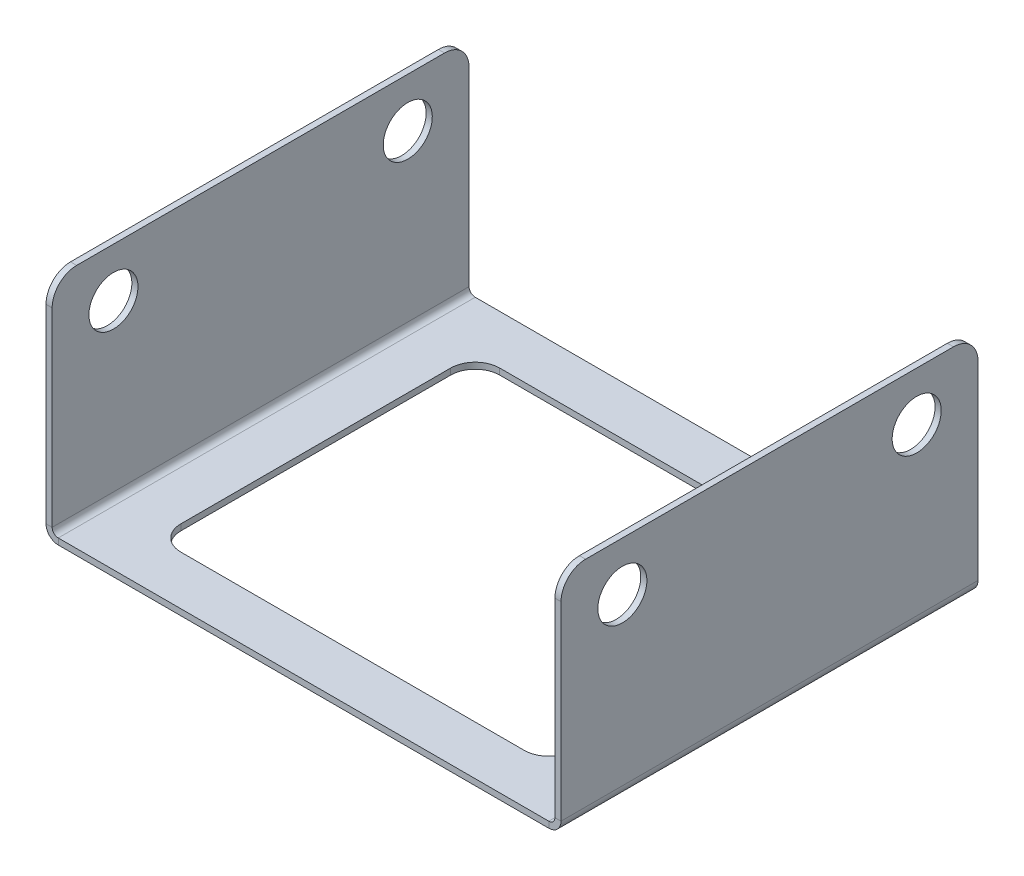
SolidWorks part; units mm, degrees
note: The reader was unsure of these and kept them because the rebuilt part matched: flange length of "Edge-Flange2", "Edge-Flange3".
ref_plane "Front Plane" through (0, 0, 0) normal (0, 0, 1) x (1, 0, 0)
ref_plane "Top Plane" through (0, 0, 0) normal (0, 1, 0) x (1, 0, 0)
ref_plane "Right Plane" through (0, 0, 0) normal (1, 0, 0) x (0, 0, -1)
sketch "Sketch1" plane through (0, 0, 0) normal (0, 1, 0) x (1, 0, 0)
  line L1 (-10, 8.5) -> (10, 8.5)
  line L2 (-10, 8.5) -> (-10, -8.5)
  line L3 (-10, -8.5) -> (10, -8.5)
  line L4 (10, 8.5) -> (10, -8.5)
  line L5 (-10, 8.5) -> (10, -8.5) construction
  line L6 (-10, -8.5) -> (10, 8.5) construction
  point P0 (0, 0)
base flange "Base-Flange1" sketch "Sketch1" thickness 0.25 reverse thickness direction no parameters "D1"=20
sketch "Sketch6" plane through (0, 0, 0) normal (0, 1, 0) x (1, 0, 0)
  line L1 (-7, 6.5) -> (7, 6.5)
  line L2 (-8, 5.5) -> (-8, -5.5)
  line L3 (-7, -6.5) -> (7, -6.5)
  line L4 (8, 5.5) -> (8, -5.5)
  line L5 (-8, 6.5) -> (8, -6.5) construction
  line L6 (-8, -6.5) -> (8, 6.5) construction
  arc A0 (-8, -5.5) -> (-7, -6.5) centre (-7, -5.5) ccw
  arc A1 (7, -6.5) -> (8, -5.5) centre (7, -5.5) ccw
  arc A2 (8, 5.5) -> (7, 6.5) centre (7, 5.5) ccw
  arc A3 (-7, 6.5) -> (-8, 5.5) centre (-7, 5.5) ccw
  point P0 (0, 0)
  dimension "D1" = 1
extrude "Cut-Extrude1" cut sketch "Sketch6" against normal through all normal cut yes
edge flange "Edge-Flange2" sketch "Sketch18" flange angle 90 flange length 9 flange position bend outside bend radius 0.25 thickness 0.25 parameters "D6"=10
sketch "Sketch18" plane through (10, 0, 0) normal (1, 0, 0) x (0, 0, -1)
  line L0 (-8.5, 0) -> (8.5, 0) construction
  line L1 (-8.5, 0) -> (8.5, 0)
  line L2 (-8.5, 0) -> (-8.5, 9)
  line L3 (-8.5, 9) -> (8.5, 9)
  line L4 (8.5, 9) -> (8.5, 0)
bend "EdgeBend1" bend radius 0.25 bend angle 90 parameters "D5"=1
edge flange "Edge-Flange3" sketch "Sketch23" flange angle 90 flange length 9 flange position bend outside bend radius 0.25 thickness 0.25 parameters "D6"=10
sketch "Sketch23" plane through (-10, 0, 0) normal (1, 0, 0) x (0, 0, -1)
  line L1 (8.5, 0) -> (-8.5, 0) construction
  line L2 (-8.5, 0) -> (-8.5, 9)
  line L3 (-8.5, 9) -> (8.5, 9)
  line L4 (8.5, 9) -> (8.5, 0)
  line L5 (8.5, 0) -> (-8.5, 0)
bend "EdgeBend2" bend radius 0.25 bend angle 90 parameters "D5"=2
fillet "Fillet1" radius 1 4 edges at (-10.375, 9, 8.5) (-10.375, 9, -8.5) (10.375, 9, -8.5) (10.375, 9, 8.5)
sketch "Sketch27" plane through (-10.5, 0, 0) normal (-1, 0, 0) x (0, 0, 1)
  line L0 (0, 9) -> (0, 10.9856) construction
  line L2 (0, 7) -> (3.9115, 7) construction
  line L3 (-6.6726, 9) -> (-10.6194, 9) construction
  line L6 (-5, 7) -> (-5, 10.8971) construction
  circle A0 centre (-6, 7) radius 1
  circle A1 centre (6, 7) radius 1
  dimension "D2" = 6
  dimension "D1" = 2
extrude "Cut-Extrude2" cut sketch "Sketch27" against normal through all normal cut yes
sketch "Bend-Lines1" [suppressed] plane through (0, 0, 0) normal (0, 1, 0) x (1, 0, 0)
sketch "Bounding-Box1" [suppressed] plane through (0, 0, 0) normal (0, 1, 0) x (1, 0, 0)
sheet metal parameters "Sheet-Metal(1)" thickness 0.25 parameters "D1"=20
flat pattern "Flat-Pattern(1)" [suppressed]
sketch "Bend-Lines2" plane through (0, 0, 0) normal (0, 1, 0) x (1, 0, 0)
sketch "Bounding-Box2" [suppressed] plane through (0, 0, 0) normal (0, 1, 0) x (1, 0, 0)
sheet metal parameters "Sheet-Metal(2)" thickness 0.25 parameters "D1"=20
flat pattern "Flat-Pattern(1)"
sketch "Bend-Lines3" plane through (0, 0, 0) normal (0, 1, 0) x (1, 0, 0)
sketch "Bounding-Box3" [suppressed] plane through (0, 0, 0) normal (0, 1, 0) x (1, 0, 0)
sheet metal parameters "Sheet-Metal(3)" thickness 0.25 parameters "D1"=20
flat pattern "Flat-Pattern(1)" [suppressed]
sketch "Bend-Lines4" plane through (0, 0, 0) normal (0, 1, 0) x (1, 0, 0)
sketch "Bounding-Box4" [suppressed] plane through (0, 0, 0) normal (0, 1, 0) x (1, 0, 0)
bend of the flat pattern "Flatten-<EdgeBend1>1"
sheet metal parameters "Sheet-Metal(4)" thickness 0.25 parameters "D1"=20
flat pattern "Flat-Pattern(1)" [suppressed]
sketch "Bend-Lines5" plane through (0, 0, 0) normal (0, 1, 0) x (1, 0, 0)
sketch "Bounding-Box5" [suppressed] plane through (0, 0, 0) normal (0, 1, 0) x (1, 0, 0)
bend of the flat pattern "Flatten-<EdgeBend1>2"
bend of the flat pattern "Flatten-<EdgeBend2>1"
sheet metal parameters "Sheet-Metal(5)" thickness 0.25 parameters "D1"=20
flat pattern "Flat-Pattern(1)"
sketch "Bend-Lines6" plane through (0, 0, 0) normal (0, 1, 0) x (1, 0, 0)
  line L0 (-10.2945, 8.5) -> (-10.2945, -8.5) construction
  line L1 (10.2945, -8.5) -> (10.2945, 8.5) construction
  line L2 (-10.2945, 8.5) -> (-10.2945, -8.5) construction
  line L3 (10.2945, -8.5) -> (10.2945, 8.5) construction
sketch3d "Bounding-Box6" [suppressed]
  line L0 (19.339, -8.5, 0) -> (-19.339, -8.5, 0) construction
  line L1 (19.339, 8.5, 0) -> (-19.339, 8.5, 0) construction
  line L2 (19.339, -8.5, 0) -> (19.339, 8.5, 0) construction
  line L3 (-19.339, -8.5, 0) -> (-19.339, 8.5, 0) construction
bend of the flat pattern "Flatten-<EdgeBend1>3"
bend of the flat pattern "Flatten-<EdgeBend2>2"
